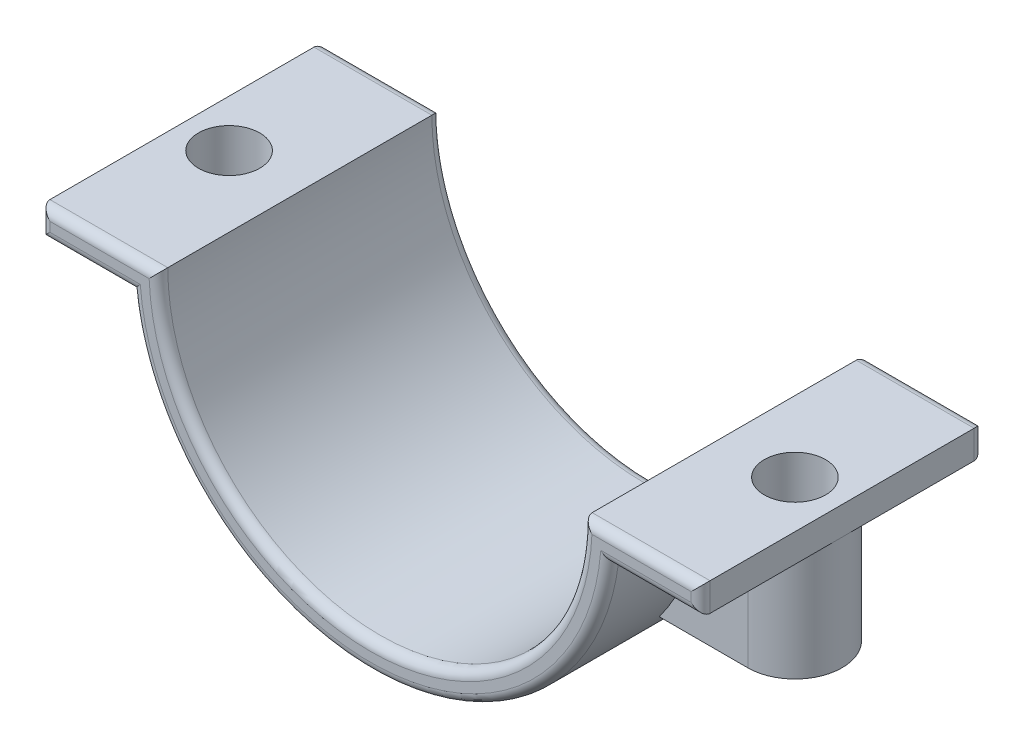
SolidWorks part; units mm, degrees
ref_plane "Front Plane" through (0, 0, 0) normal (0, 0, 1) x (1, 0, 0)
ref_plane "Top Plane" through (0, 0, 0) normal (0, 1, 0) x (1, 0, 0)
ref_plane "Right Plane" through (0, 0, 0) normal (1, 0, 0) x (0, 0, -1)
sketch "Sketch1" plane through (0, 0, 0) normal (0, 0, 1) x (1, 0, 0)
  line L0 (-35, 0) -> (-22.5, 0)
  line L1 (22.5, 0) -> (35, 0)
  line L2 (-35, -3) -> (-25.3229, -3)
  line L3 (25.3229, -3) -> (35, -3)
  line L4 (-35, 0) -> (-35, -3)
  line L5 (35, 0) -> (35, -3)
  arc A0 (-22.5, 0) -> (22.5, 0) centre (0, 0) ccw
  arc A1 (-25.3229, -3) -> (25.3229, -3) centre (0, 0) ccw
  dimension "D1" = 22.5
  dimension "D2" = 35
  dimension "D3" = 3
extrude "Boss-Extrude1" add sketch "Sketch1" along normal mid plane 30
sketch "Sketch2" plane through (0, -3, 0) normal (0, -1, 0) x (1, 0, 0)
  line L0 (35, 15) -> (35, -15) construction
  line L1 (18, 5) -> (30, 5)
  line L2 (18, 5) -> (18, -5)
  line L3 (18, -5) -> (30, -5)
  line L4 (30, 5) -> (30, -5)
  line L5 (18, 5) -> (30, -5) construction
  line L6 (18, -5) -> (30, 5) construction
  circle A0 centre (30, 0) radius 5
  circle A1 centre (30, 0) radius 3.25
  point P0 (24, 0)
  line M9 (25.3229, 15) -> (25.3229, -15)
  dimension "D1" = 10
  dimension "D3" = 6.5
  dimension "D2" = 12
extrude "Boss-Extrude2" add sketch "Sketch2" against normal up to body from offset 12 contours A0 L1 L2 L3 M9 | L4 A1 | A0 L3 M9 | A0 L1 M9 | L4 A1 | A0 region at (21.6241, -3, 0) region at (26.4044, -3, 4.1253) region at (26.4044, -3, -4.1253) region at (31.3793, -3, 0) region at (28.6207, -3, 0)
extrude "Cut-Extrude1" cut sketch "Sketch2<3>" against normal through all contours L4 A1 | L4 A1 region at (31.3793, -3, 0) region at (28.6207, -3, 0)
sketch "Sketch2<3>" plane through (0, -3, 0) normal (0, -1, 0) x (1, 0, 0) same geometry as "Sketch2"
mirror "Mirror1" about plane through (0, 0, 0) normal (1, 0, 0) of "Boss-Extrude2", "Cut-Extrude1"
fillet "Fillet1" radius 1 16 edges at (-30.1615, -3, -15) (0, -25.5, -15) (30.1615, -3, -15) (35, -1.5, -15) (28.75, 0, -15) (0, -22.5, -15) (-28.75, 0, -15) (-35, -1.5, -15) (-28.75, 0, 15) (0, -22.5, 15) (28.75, 0, 15) (35, -1.5, 15) (30.1615, -3, 15) (0, -25.5, 15) (-30.1615, -3, 15) (-35, -1.5, 15)
